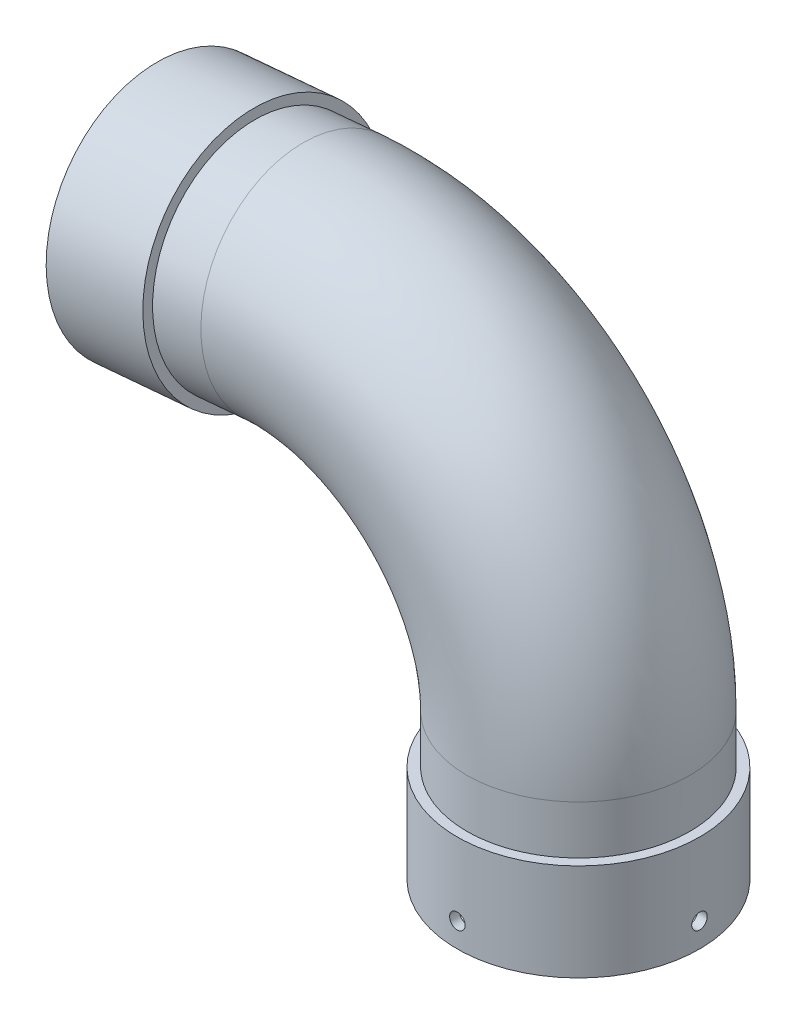
SolidWorks part; units mm, degrees
ref_plane "前视基准面" through (0, 0, 0) normal (0, 0, 1) x (1, 0, 0)
ref_plane "上视基准面" through (0, 0, 0) normal (0, 1, 0) x (1, 0, 0)
ref_plane "右视基准面" through (0, 0, 0) normal (1, 0, 0) x (0, 0, -1)
sketch "草图1" plane through (0, 0, 0) normal (0, 1, 0) x (1, 0, 0)
  circle A0 centre (0, 0) radius 21
  circle A1 centre (0, 0) radius 23
  dimension "D1" = 42
  dimension "D2" = 46
sketch "草图2" plane through (0, 0, 0) normal (0, 0, 1) x (1, 0, 0)
  line L0 (0, 0) -> (0, 20)
  line L3 (-54.733, 70.1535) -> (-74.6569, 68.4104)
  arc A0 (-54.733, 70.1535) -> (0, 20) centre (-50.3451, 20) cw
  dimension "D2" = 85
  dimension "D1" = 20
sweep "扫描1" add profiles "草图1" path "草图2"
sketch "草图3" plane through (0, 0, 0) normal (0, -1, 0) x (1, 0, 0)
  circle A0 centre (0, 0) radius 23
  circle A1 centre (0, 0) radius 25
  dimension "D1" = 46
  dimension "D2" = 50
extrude "凸台-拉伸1" add sketch "草图3" along normal blind 10 and the other way blind 10 separate body
sketch "草图4" plane through (-68.1501, -5.9624, 0) normal (-0.9962, -0.0872, 0) x (0, 0, 1)
  circle A0 centre (0, 74.6569) radius 23
  circle A1 centre (0, 74.6569) radius 25
  dimension "D1" = 46
  dimension "D2" = 50
extrude "凸台-拉伸2" add sketch "草图4" along normal blind 10 and the other way blind 10
sketch "草图5" plane through (0, 0, 0) normal (0, 0, 1) x (1, 0, 0)
  line L0 (0, -10) -> (0, 0) construction
  line L6 (-23, 0) -> (23, 0) construction
  line L7 (-23, -10) -> (23, -10) construction
  circle A2 centre (0, -5) radius 1.6
  dimension "D1" = 3.2
extrude "切除-拉伸1" cut sketch "草图5" against normal through all and the other way through all
sketch "草图7" plane through (0, 0, 0) normal (1, 0, 0) x (0, 0, -1)
  line L0 (0, 0) -> (0, -10) construction
  line L1 (-23, 0) -> (23, 0) construction
  line L2 (-23, -10) -> (23, -10) construction
  circle A0 centre (0, -5) radius 1.6
  dimension "D1" = 3.2
extrude "切除-拉伸2" cut sketch "草图7" against normal through all and the other way through all
